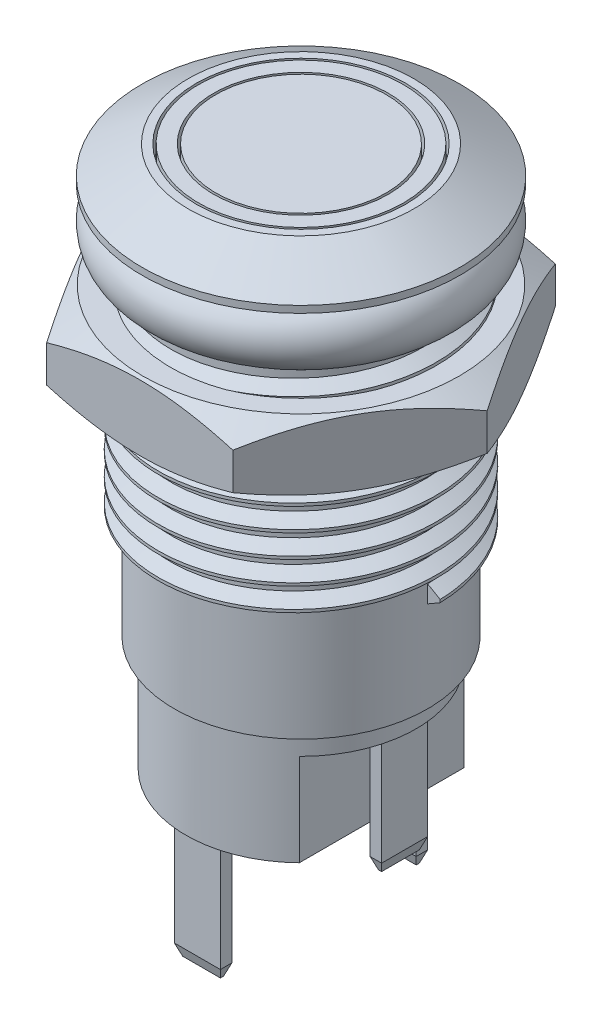
SolidWorks part; units mm, degrees
ref_plane "Спереди" through (0, 0, 0) normal (0, 0, 1) x (1, 0, 0)
ref_plane "Сверху" through (0, 0, 0) normal (0, 1, 0) x (1, 0, 0)
ref_plane "Справа" through (0, 0, 0) normal (1, 0, 0) x (0, 0, -1)
sketch "Эскиз1" plane through (0, 0, 0) normal (0, 0, 1) x (1, 0, 0)
  line L0 (0, 0) -> (0, 23.5) construction
  line L1 (0, 23.5) -> (4.9, 23.5)
  line L2 (4.9, 23.5) -> (6.9, 22.3)
  line L3 (6.9, 22.3) -> (6.9, 22)
  line L5 (5.5, 19.2) -> (5.5, 5)
  line L6 (5.5, 5) -> (5, 5)
  line L7 (5, 5) -> (5, 0)
  line L8 (5, 0) -> (0, 0)
  line L9 (6.9, 22) -> (5.5, 22)
  line L10 (0, 0) -> (0, 23.5)
  line L11 (0, 23.5) -> (0, 0) construction
  arc A1 (5.5, 22) -> (5.5, 19.2) centre (5.5, 20.6) cw
  dimension "D1" = 9.8
  dimension "D2" = 1.5
  dimension "D5" = 11
  dimension "D3" = 13.8
  dimension "D4" = 0.3
  dimension "D6" = 5
  dimension "D7" = 23.5
  dimension "D8" = 10
revolve "Повернуть1" add sketch "Эскиз1" angle 360 about L10
sketch "Эскиз2" plane through (0, 0, 0) normal (0, 0, 1) x (1, 0, 0)
  line L1 (3.5, 4) -> (5, 4)
  line L2 (3.5, 4) -> (3.5, 0)
  line L3 (3.5, 0) -> (5, 0)
  line L4 (5, 4) -> (5, 0)
  line L5 (3.5, 4) -> (5, 0) construction
  line L6 (3.5, 0) -> (5, 4) construction
  line L7 (-5, 0) -> (5, 0) construction
  line L8 (-5, 4) -> (-3.5, 4)
  line L9 (-5, 4) -> (-5, 0)
  line L10 (-5, 0) -> (-3.5, 0)
  line L11 (-3.5, 4) -> (-3.5, 0)
  line L12 (-5, 4) -> (-3.5, 0) construction
  line L13 (-5, 0) -> (-3.5, 4) construction
  line L14 (-5, 5) -> (-5, 0) construction
  line L15 (5, 0) -> (5, 5) construction
  point P4 (4.25, 2)
  point P12 (-4.25, 2)
  dimension "D1" = 7
  dimension "D2" = 4
extrude "Вырез-Вытянуть1" cut sketch "Эскиз2" against normal through all both and the other way through all
thread "Резьба1" pitch 1 method extrude profile "Профиль резьбы1" start angle 0, offset 0, length 9.5, pitch 1, diameter 11
ref_plane "Плоскость1" through (-5.5, 19.2, 0) normal (0, 0, 1) x (-1, 0, 0)
sketch "Профиль резьбы1" plane through (-5.5, 19.2, 0) normal (0, 0, 1) x (-1, 0, 0)
  line L0 (0, 0) -> (0, 1) construction
  line L1 (0, 0) -> (0.5413, 0.3125)
  line L2 (0.5413, 0.3125) -> (0.5413, 0.4375)
  line L3 (0.5413, 0.4375) -> (0, 0.75)
  line L4 (0.5413, 0.375) -> (0, 0.375) construction
  line L11 (0, 0) -> (0, 0.75)
  point P2 (0, 0)
  dimension "Pitch" = 1
  dimension "Profile_Angle" = 60
  dimension "Profile_Land" = 0.125
  dimension "Profile_Height" = 0.5413
sketch "Эскиз5" plane through (0, 4, 0) normal (0, -1, 0) x (1, 0, 0)
  line L0 (3.5, -3.5707) -> (3.5, 3.5707) construction
  line L1 (4, 1) -> (4.5, 1)
  line L2 (4, 1) -> (4, -1)
  line L3 (4, -1) -> (4.5, -1)
  line L4 (4.5, 1) -> (4.5, -1)
  line L5 (4, 1) -> (4.5, -1) construction
  line L6 (4, -1) -> (4.5, 1) construction
  circle A0 centre (0, 0) radius 4.25 construction
  point P4 (4.25, 0)
  dimension "D1" = 0.5
  dimension "D2" = 2
  dimension "D3" = 0.5
extrude "Бобышка-Вытянуть1" add sketch "Эскиз5" along normal blind 5.3
chamfer "Фаска1" distance 0.5 angle 20 4 edges at (4.25, -1.3, 1) (4, -1.3, 0) (4.25, -1.3, -1) (4.5, -1.3, 0) first distance on face at (4.25, 1.35, 1) first distance on face at (4, 1.35, 0) first distance on face at (4.25, 1.35, -1) first distance on face at (4.5, 1.35, 0)
pattern_circular "Круговой массив1" count 2 over 360 about axis through (0, 0, 0) along (0, -1, 0) of "Фаска1", "Бобышка-Вытянуть1"
ref_plane "Плоскость2" through (0, 18.2, 0) normal (0, 1, 0) x (1, 0, 0)
sketch "Эскиз6" plane through (0, 18.2, 0) normal (0, 1, 0) x (1, 0, 0)
  line L1 (8.0829, 0) -> (4.0415, 7)
  line L2 (4.0415, 7) -> (-4.0415, 7)
  line L3 (-4.0415, 7) -> (-8.0829, 0)
  line L4 (-8.0829, 0) -> (-4.0415, -7)
  line L5 (-4.0415, -7) -> (4.0415, -7)
  line L6 (4.0415, -7) -> (8.0829, 0)
  circle A0 centre (0, 0) radius 7 construction
  dimension "D1" = 14
extrude "Бобышка-Вытянуть2" add sketch "Эскиз6" against normal blind 3
sketch "Эскиз7" plane through (0, 0, 0) normal (0, 0, 1) x (1, 0, 0)
  line L0 (-8.0829, 18.2) -> (-8.0829, 17.5)
  line L2 (-8.0829, 17.5) -> (-6.8705, 18.2)
  line L3 (4.0415, 18.2) -> (8.0829, 18.2) construction
  line L4 (-6.8705, 18.2) -> (-8.0829, 18.2)
  line L5 (-8.0829, 15.9) -> (-8.0829, 15.2)
  line L6 (-8.0829, 15.2) -> (-6.8705, 15.2)
  line L7 (4.0415, 15.2) -> (8.0829, 15.2) construction
  line L9 (-8.0829, 15.2) -> (-4.0415, 15.2) construction
  line L10 (-8.0829, 15.9) -> (-6.8705, 15.2)
  line L11 (-8.0829, 15.2) -> (-8.0829, 18.2) construction
  dimension "D1" = 30
  dimension "D2" = 0.7
revolve "Вырез-Повернуть1" cut sketch "Эскиз7" angle 360 about L10 region at (-7.6788, 17.9667, 0) region at (-7.6788, 15.4333, 0)
sketch "Эскиз8" plane through (0, 0, 0) normal (0, -1, 0) x (1, 0, 0)
  line L0 (4, 1) -> (4.5, 1) construction
  line L1 (-1, 4.5) -> (1, 4.5)
  line L2 (-1, 4.5) -> (-1, 4)
  line L3 (-1, 4) -> (1, 4)
  line L4 (1, 4.5) -> (1, 4)
  line L5 (-1, 4.5) -> (1, 4) construction
  line L6 (-1, 4) -> (1, 4.5) construction
  line L7 (4, 1) -> (4, -1) construction
  circle A0 centre (0, 0) radius 4.25 construction
  point P4 (0, 4.25)
extrude "Бобышка-Вытянуть3" add sketch "Эскиз8" along normal blind 5.3
chamfer "Фаска2" distance 0.5 angle 20 4 edges at (-1, -5.3, 4.25) (0, -5.3, 4) (1, -5.3, 4.25) (0, -5.3, 4.5) first distance on face at (-1, -2.65, 4.25) first distance on face at (0, -2.65, 4) first distance on face at (1, -2.65, 4.25) first distance on face at (0, -2.65, 4.5)
pattern_circular "Круговой массив2" count 2 over 360 about axis through (0, 0, 0) along (0, -1, 0) of "Бобышка-Вытянуть3", "Фаска2" reverse direction yes
sketch "Эскиз9" plane through (0, 23.5, 0) normal (0, 1, 0) x (1, 0, 0)
  circle A0 centre (0, 0) radius 4.5
  circle A1 centre (0, 0) radius 3.75
  dimension "D1" = 9
  dimension "D2" = 7.5
extrude "Вырез-Вытянуть-Тонкостенный1" cut sketch "Эскиз9" against normal blind 1 thin contours A0 | A1 thin type mid plane wall 0.1
